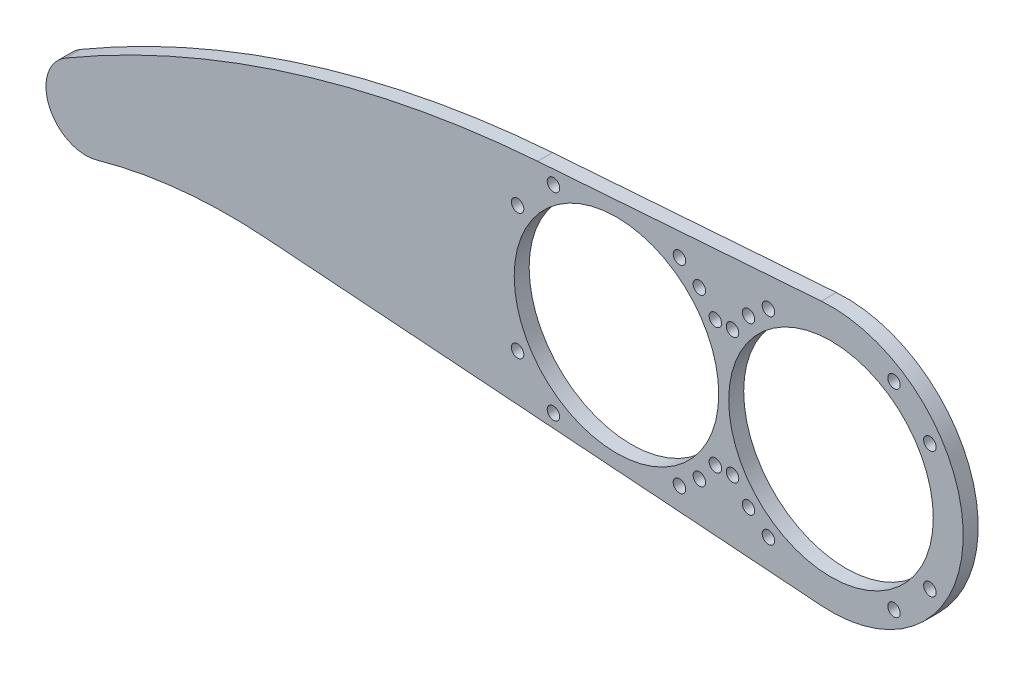
SolidWorks part; units mm, degrees
ref_plane "前视基准面" through (0, 0, 0) normal (0, 0, 1) x (1, 0, 0)
ref_plane "上视基准面" through (0, 0, 0) normal (0, 1, 0) x (1, 0, 0)
ref_plane "右视基准面" through (0, 0, 0) normal (1, 0, 0) x (0, 0, -1)
other "Configuration Table"
sketch "草图1" plane through (0, 0, 0) normal (0, 0, 1) x (1, 0, 0)
  line L0 (-74.3846, 0) -> (17.4339, 0) construction
  line L1 (0, 31.8895) -> (0, -25.7876) construction
  line L3 (43.9593, -12.49) -> (43.9593, 12.49) construction
  line L4 (33.9493, 22.5) -> (-34.0307, 22.5) construction
  line L5 (-44.0407, 12.49) -> (-44.0407, -12.49) construction
  line L6 (-34.0307, -22.5) -> (33.9493, -22.5) construction
  line L10 (19.5268, 26.4294) -> (-37.3585, 22.27)
  line L11 (19.5268, -26.4294) -> (-91.9284, -18.2799)
  arc A0 (43.9593, 12.49) -> (43.0291, 15.3946) centre (38.9593, 12.49) ccw construction
  arc A1 (43.0291, 15.3946) -> (36.854, 21.5698) centre (21.4593, 0) ccw construction
  arc A2 (36.854, 21.5698) -> (33.9493, 22.5) centre (33.9493, 17.5) ccw construction
  arc A3 (-34.0307, 22.5) -> (-36.9353, 21.5698) centre (-34.0307, 17.5) ccw construction
  arc A4 (-36.9353, 21.5698) -> (-43.1105, 15.3946) centre (-21.5407, 0) ccw construction
  arc A5 (-43.1105, 15.3946) -> (-44.0407, 12.49) centre (-39.0407, 12.49) ccw construction
  arc A6 (-44.0407, -12.49) -> (-43.1105, -15.3946) centre (-39.0407, -12.49) ccw construction
  arc A7 (-43.1105, -15.3946) -> (-36.9353, -21.5698) centre (-21.5407, 0) ccw construction
  arc A8 (-36.9353, -21.5698) -> (-34.0307, -22.5) centre (-34.0307, -17.5) ccw construction
  arc A9 (33.9493, -22.5) -> (36.854, -21.5698) centre (33.9493, -17.5) ccw construction
  arc A10 (36.854, -21.5698) -> (43.0291, -15.3946) centre (21.4593, 0) ccw construction
  arc A11 (43.0291, -15.3946) -> (43.9593, -12.49) centre (38.9593, -12.49) ccw construction
  circle A12 centre (-34.1672, 19.7847) radius 1.25
  circle A13 centre (-41.3604, 12.5915) radius 1.25
  circle A14 centre (-41.3604, -12.6616) radius 1.25
  circle A15 centre (-8.9141, 19.7847) radius 1.25
  circle A16 centre (-4.9237, 16.582) radius 1.25
  circle A17 centre (-1.721, 12.5915) radius 1.25
  circle A18 centre (-1.721, -12.6616) radius 1.25
  circle A19 centre (-4.9237, -16.6521) radius 1.25
  circle A20 centre (-8.9141, -19.8547) radius 1.25
  circle A21 centre (-34.1672, -19.8547) radius 1.25
  circle A22 centre (34.0859, -19.8547) radius 1.25
  circle A23 centre (41.279, -12.6616) radius 1.25
  circle A24 centre (41.279, 12.5915) radius 1.25
  circle A25 centre (34.0859, 19.7847) radius 1.25
  circle A36 centre (21.4593, 0) radius 20.5
  arc A37 (0.1141, 15.7045) -> (0, 15.5482) centre (21.4593, 0) ccw
  circle A39 centre (-21.5407, 0) radius 20.5
  arc A41 (0.1141, 15.7045) -> (0, 15.5482) centre (21.4593, 0) ccw
  arc A44 (0.1141, 15.7045) -> (0, 15.5482) centre (21.4593, 0) ccw
  arc A45 (-37.3585, 22.27) -> (-131.9244, -7.0942) centre (-21.3909, -196.1075) ccw
  arc A46 (-91.9284, -18.2799) -> (-125.7155, -21.6999) centre (-99.0862, -116.1709) ccw
  arc A47 (-131.9244, -7.0942) -> (-125.7155, -21.6999) centre (-127.8859, -14) ccw
  circle A48 centre (8.9141, -19.8547) radius 1.25
  arc A49 (19.5268, -26.4294) -> (19.5268, 26.4294) centre (21.4593, 0) ccw
  circle A50 centre (4.9237, -16.6521) radius 1.25
  circle A51 centre (1.721, -12.6616) radius 1.25
  circle A52 centre (8.9141, 19.7847) radius 1.25
  circle A53 centre (4.9237, 16.582) radius 1.25
  circle A54 centre (1.721, 12.5915) radius 1.25
  dimension "D3" = 41
  dimension "D4" = 8
  dimension "D2" = 150
  dimension "D5" = 14
extrude "凸台-拉伸1" add sketch "草图1" along normal blind 3 contours A12 A13 A14 A15 A16 A17 A18 A19 A20 A21 A22 A23 A24 A25 A36 region at (-51.3437, -2.2561, 0)
